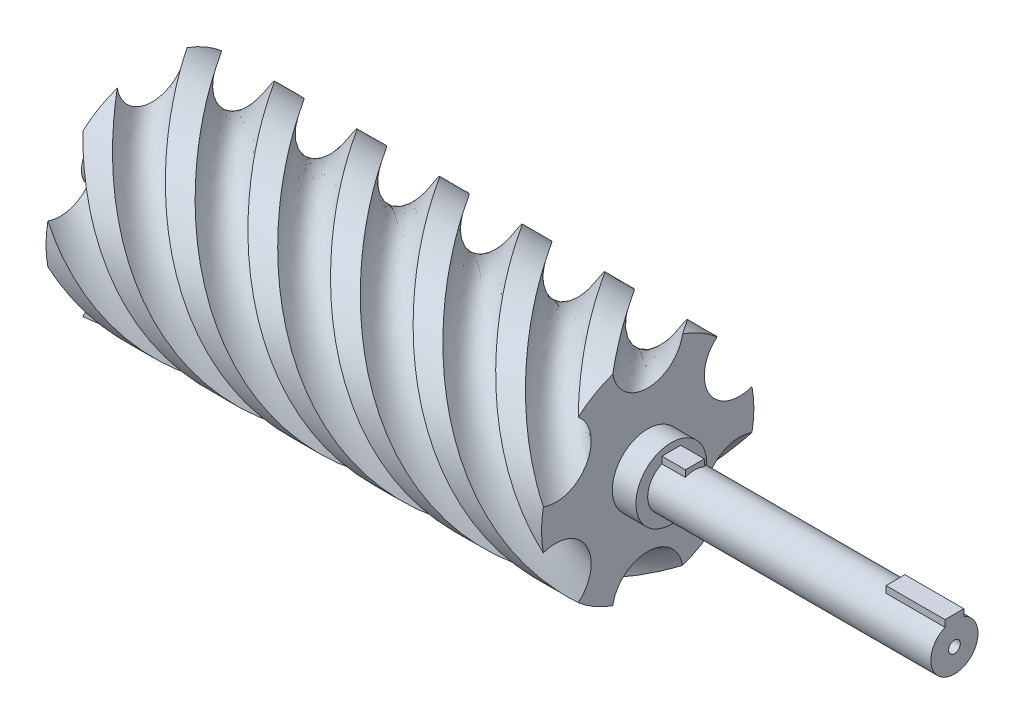
SolidWorks part; units mm, degrees
material "Cast Alloy Steel"
ref_plane "Front Plane" through (0, 0, 0) normal (0, 0, 1) x (1, 0, 0)
ref_plane "Top Plane" through (0, 0, 0) normal (0, 1, 0) x (1, 0, 0)
ref_plane "Right Plane" through (0, 0, 0) normal (1, 0, 0) x (0, 0, -1)
sketch "Sketch1" plane through (0, 0, 0) normal (1, 0, 0) x (0, 0, -1)
  line L0 (0, 0) -> (0, 60) construction
  line L1 (0, 0) -> (51.9615, -30) construction
  line L2 (0, 0) -> (-51.9615, -30) construction
  line L3 (-38.9711, 22.5) -> (0, 0) construction
  line L4 (0, 0) -> (38.9711, 22.5) construction
  circle A0 centre (0, 0) radius 60 construction
  arc A1 (-29.411, -34.0587) -> (-14.7902, -42.5) centre (0, 0) ccw
  circle A2 centre (0, 45) radius 15 construction
  circle A3 centre (38.9711, -22.5) radius 15 construction
  circle A4 centre (-38.9711, -22.5) radius 15 construction
  circle A8 centre (38.9711, 22.5) radius 15 construction
  circle A9 centre (0, -45) radius 15 construction
  circle A10 centre (-38.9711, 22.5) radius 15 construction
  arc A11 (-14.7902, 42.5) -> (14.7902, 42.5) centre (0, 45) ccw
  arc A12 (29.411, 34.0587) -> (44.2012, 8.4413) centre (38.9711, 22.5) ccw
  arc A13 (44.2012, -8.4413) -> (29.411, -34.0587) centre (38.9711, -22.5) ccw
  arc A14 (14.7902, -42.5) -> (-14.7902, -42.5) centre (0, -45) ccw
  arc A15 (-29.411, -34.0587) -> (-44.2012, -8.4413) centre (-38.9711, -22.5) ccw
  arc A16 (14.7902, -42.5) -> (29.411, -34.0587) centre (0, 0) ccw
  arc A17 (-44.2012, 8.4413) -> (-29.411, 34.0587) centre (-38.9711, 22.5) ccw
  arc A18 (44.2012, -8.4413) -> (44.2012, 8.4413) centre (0, 0) ccw
  arc A19 (29.411, 34.0587) -> (14.7902, 42.5) centre (0, 0) ccw
  arc A20 (-14.7902, 42.5) -> (-29.411, 34.0587) centre (0, 0) ccw
  arc A21 (-44.2012, 8.4413) -> (-44.2012, -8.4413) centre (0, 0) ccw
  dimension "D1" = 120
  dimension "D2" = 90
  dimension "D5" = 60
  dimension "D3" = 120
  dimension "D4" = 120
  dimension "D6" = 60
sketch "Sketch2" plane through (0, 0, 0) normal (1, 0, 0) x (0, 0, -1)
  circle A0 centre (0, 0) radius 60
  dimension "D1" = 120
curve "Helix/Spiral1" pitch 210 height 210 radius 60 centre (0, 0, 0) axis (1, 0, 0) start towards (0, 1, 0)
sweep "Sweep1" add profiles "Sketch1" path "Helix/Spiral1"
sketch "Sketch3" plane through (0, 0, 0) normal (1, 0, 0) x (0, 0, -1)
  circle A0 centre (0, 0) radius 10
  dimension "D1" = 20
extrude "Boss-Extrude1" add sketch "Sketch3" along normal blind 340 and the other way blind 20
sketch "Sketch4" plane through (210, 0, 0) normal (1, 0, 0) x (0, 0, -1)
  circle A0 centre (0, 0) radius 15
  dimension "D1" = 30
extrude "Boss-Extrude2" add sketch "Sketch4" along normal blind 10
sketch "Sketch5" plane through (220, 0, 0) normal (1, 0, 0) x (0, 0, -1)
  line L1 (-4, 5) -> (4, 5)
  line L2 (-4, 5) -> (-4, 12)
  line L3 (-4, 12) -> (4, 12)
  line L4 (4, 5) -> (4, 12)
  point P4 (0, 12)
  dimension "D1" = 8
  dimension "D2" = 12
  dimension "D3" = 7
extrude "Boss-Extrude3" add sketch "Sketch5" along normal blind 10
sketch "Sketch6" plane through (340, 0, 0) normal (1, 0, 0) x (0, 0, -1)
  line L0 (4, 12) -> (-4, 12)
  line L1 (-4, 12) -> (-4, 5.7163)
  line L2 (-4, 5.7163) -> (4, 5.7163)
  line L3 (4, 5.7163) -> (4, 12)
extrude "Boss-Extrude4" add sketch "Sketch6" against normal blind 25
hole_wizard "Tap Drill for M6 Tap1" positions "Sketch7" profile "Sketch8" hole size "M6" standard "ISO"
sketch "Sketch7" plane through (340, 0, 0) normal (1, 0, 0) x (0, 0, -1)
  point P0 (0, 0)
sketch "Sketch8" plane through (340, 0, 0) normal (0, 1, 0) x (0, 0, -1)
  line L0 (0, 0) -> (0, 21.5022)
  line L1 (0, 21.5022) -> (2.5, 20)
  line L2 (2.5, 20) -> (2.5, 0)
  line L5 (2.5, 0) -> (0, 0)
  line L10 (0, 21.5022) -> (-2.5, 20) construction
  line L11 (0, -6.35) -> (0, 107.95) construction
  dimension "Hole Dia." = 5
  dimension "Hole Depth" = 20
  dimension "Drill Angle" = 118
